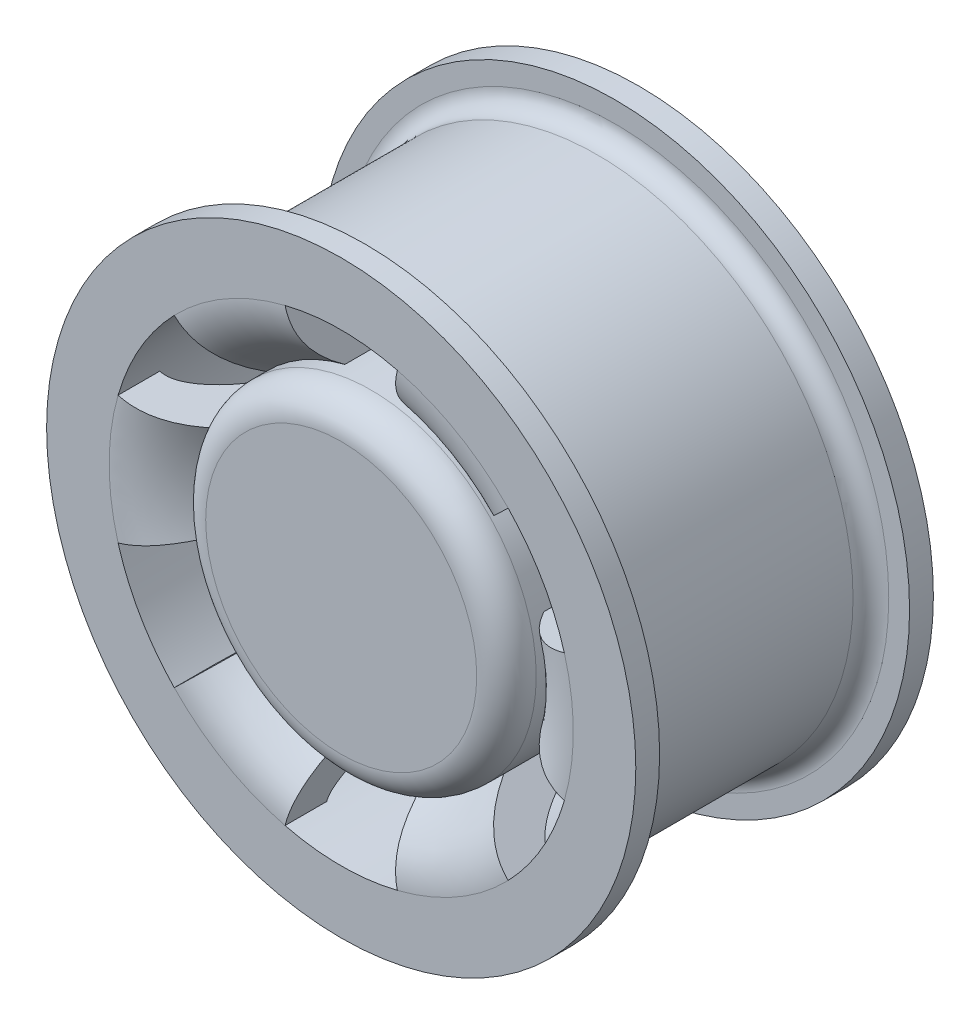
SolidWorks part; units mm, degrees
material "2024 Сплав"
ref_plane "Спереди" through (0, 0, 0) normal (0, 0, 1) x (1, 0, 0)
ref_plane "Сверху" through (0, 0, 0) normal (0, 1, 0) x (1, 0, 0)
ref_plane "Справа" through (0, 0, 0) normal (1, 0, 0) x (0, 0, -1)
sketch "Эскиз1" plane through (0, 0, 0) normal (0, 1, 0) x (1, 0, 0)
  line L0 (0, 0) -> (0, 47.4199) construction
  line L1 (0, 0) -> (79.812, 0) construction
  line L2 (39, 25) -> (39, -18)
  line L3 (39, -25) -> (47, -25)
  line L5 (49.5, -21) -> (46, -21)
  line L6 (43, -18) -> (43, 18)
  line L9 (39, 25) -> (47, 25)
  line L10 (40.0579, -25) -> (51.9421, -25) construction
  line L11 (20.5, 0) -> (27.7696, 0)
  line L13 (47, -25) -> (49.5, -25)
  line L14 (49.5, -25) -> (49.5, -21)
  line L15 (46, 21) -> (49.5, 21)
  line L16 (49.5, 21) -> (49.5, 25)
  line L17 (49.5, 25) -> (47, 25)
  arc A0 (46, -21) -> (43, -18) centre (46, -18) cw
  arc A1 (46, 21) -> (43, 18) centre (46, 18) ccw
  spline S0 degree 3 poles (39, -25) (27.4862, -25) (22.2386, -6.3236) (20.5, 0) knots 0 0 0 0 1 1 1 1
  spline S1 degree 1 poles (39, -18) (27.2495, 1.8557) knots 0 0 1 1 construction
  spline S2 degree 3 poles (39, -18) (38.7744, -18) (38.3151, -17.9532) (37.6952, -17.7601) (36.9533, -17.3777) (35.803, -16.5242) (34.1483, -14.7283) (32.1952, -11.6157) (30.4751, -7.9745) (29.2989, -4.8534) (28.5209, -2.5054) (28.0174, -0.8635) (27.6637, 0.3644) (27.4146, 1.2563) (27.3057, 1.6516) (27.2495, 1.8557) knots 0 0 0 0 0.0625 0.125 0.1875 0.25 0.375 0.5 0.625 0.75 0.8125 0.875 0.9375 0.96875 1 1 1 1 only from (39, -18) to (27.7696, 0)
  point P3 (43, 21)
  point P12 (43, -21)
  point P16 (43, 0)
  point P19 (39.005, 0)
  dimension "D5" = 3
  dimension "D1" = 25
  dimension "D2" = 8
  dimension "D3" = 3.5
  dimension "D4" = 4
  dimension "D6" = 43
  dimension "D7" = 20.5
  dimension "D8" = 28
  dimension "D10" = 18
  dimension "D11" = 7.2696
  dimension "D12" = 4
  dimension "D13" = 3.5
  dimension "D9" = 7
revolve "Повернуть1" add sketch "Эскиз1" angle 360 about L0
sketch "Эскиз2" plane through (0, 0, 0) normal (0, 0, -1) x (-1, 0, 0)
  circle A0 centre (0, 0) radius 20.5 construction
  circle A1 centre (0, 0) radius 27.7696 construction
  circle A2 centre (0, 0) radius 20.5
  circle A3 centre (0, 0) radius 27.7696
extrude "Бобышка-Вытянуть1" add sketch "Эскиз2" against normal through all
sketch "Эскиз3" plane through (0, 0, 25) normal (0, 0, 1) x (1, 0, 0)
  circle A0 centre (0, 0) radius 27.7696 construction
  circle A1 centre (0, 0) radius 27.7696
extrude "Бобышка-Вытянуть2" add sketch "Эскиз3" against normal blind 5
sketch "Эскиз4" plane through (0, 0, 25) normal (0, 0, 1) x (1, 0, 0)
  line L0 (-6.7181, 26.9447) -> (-9.435, 37.8415)
  line L1 (6.7181, 26.9447) -> (9.435, 37.8415)
  circle A0 centre (0, 0) radius 27.7696 construction
  arc A1 (6.7181, 26.9447) -> (-6.7181, 26.9447) centre (0, 0) ccw
  circle A2 centre (0, 0) radius 39 construction
  arc A3 (9.435, 37.8415) -> (-9.435, 37.8415) centre (0, 0) ccw
  dimension "D1" = 28
extrude "Вырез-Вытянуть1" cut sketch "Эскиз4" against normal through all
pattern_circular "Круговой массив1" count 6 over 360 about axis through (0, 0, 25) along (0, 0, -1) of "Вырез-Вытянуть1"
fillet "Скругление1" radius 5 1 edges at (-27.7696, 0, 25)
sketch3d "Трехмерный эскиз1"
  line L0 (0, 0, 0) -> (-27.7696, 0, 0) construction
  arc A0 (-26.6938, 7.6543, 0) -> (-26.6938, -7.6543, 0) centre (0, 0, 0) ccw construction
  point P6 (0, 0, 27.7696)
  point P7 (-23.75, 0, 0)
  dimension "D1" = 23.75
hole_wizard "Сверление под метчик M51" positions "Эскиз11" profile "Эскиз13" hole size "M5" standard "ISO"
sketch "Эскиз11" plane through (0, 0, 0) normal (0, 0, -1) x (-1, 0, 0)
  point P0 (23.75, 0)
sketch "Эскиз13" plane through (-23.75, 0, 0) normal (1, 0, 0) x (0, 1, 0)
  line L0 (0, 0) -> (0, 23.2618)
  line L1 (0, 23.2618) -> (2.1, 22)
  line L2 (2.1, 22) -> (2.1, 0)
  line L5 (2.1, 0) -> (0, 0)
  line L10 (0, 23.2618) -> (-2.1, 22) construction
  line L11 (0, -6.35) -> (0, 107.95) construction
  dimension "Диаметр отверстия" = 4.2
  dimension "Глубина отверстия" = 22
  dimension "Угол заточки сверла" = 118
cosmetic thread "Условное изображение резьбы1" parameters "D2"=5
pattern_circular "Круговой массив3" count 6 over 360 about axis through (0, 0, 25) along (0, 0, -1) of "Сверление под метчик M51" reverse direction yes
chamfer "Фаска2" distance 0.6 angle 45 6 edges at (-13.975, -20.5681, 0) (9.775, -20.5681, 0) (21.65, 0, 0) (9.775, 20.5681, 0) (-13.975, 20.5681, 0) (-25.85, 0, 0)
